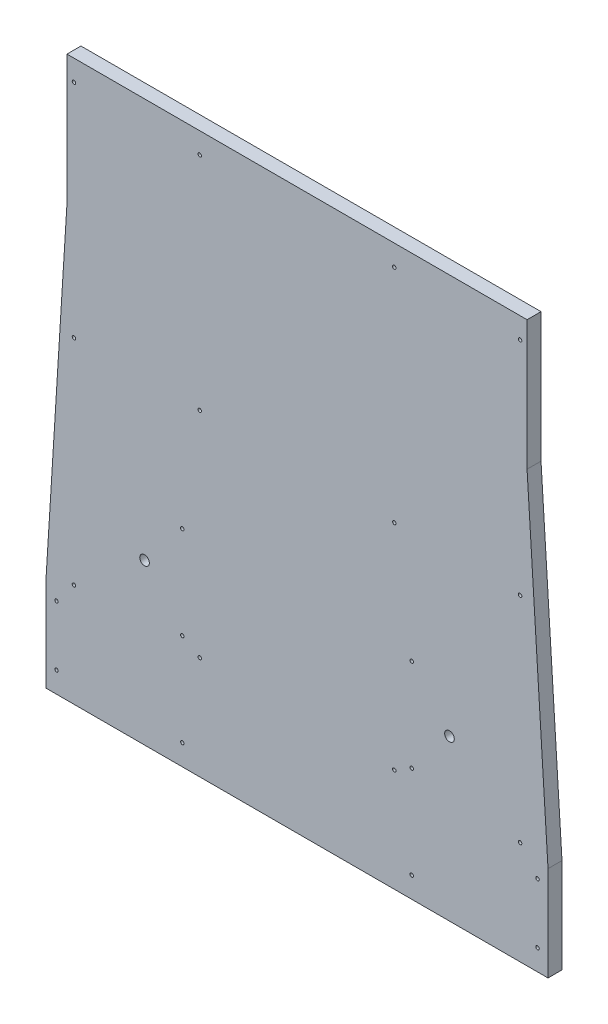
SolidWorks part; units mm, degrees
material "MDF"
ref_plane "Front Plane" through (0, 0, 0) normal (0, 0, 1) x (1, 0, 0)
ref_plane "Top Plane" through (0, 0, 0) normal (0, 1, 0) x (1, 0, 0)
ref_plane "Right Plane" through (0, 0, 0) normal (1, 0, 0) x (0, 0, -1)
sketch "Sketch1" plane through (0, 0, 0) normal (0, 0, 1) x (1, 0, 0)
  line L0 (0, -4273.1683) -> (0, -5592.0408) construction
  line L1 (209.0395, -5469.1795) -> (-209.0395, -5469.1795)
  line L2 (209.0395, -5469.1795) -> (209.0395, -5053.2545)
  line L3 (209.0395, -5053.2545) -> (-209.0395, -5053.2545)
  line L4 (0, -5469.1795) -> (0, -5053.2545) construction
  line L5 (-209.0395, -5469.1795) -> (-209.0395, -5053.2545)
  dimension "D1" = 209.0395
  dimension "D2" = 120.65
  dimension "D3" = 415.925
extrude "Boss-Extrude1" add sketch "Sketch1" along normal blind 12.7
sketch "Sketch2" plane through (0, 0, 0) normal (0, 0, -1) x (-1, 0, 0)
  line L1 (-209.0395, -5469.1795) -> (209.0395, -5469.1795)
  line L2 (-209.0395, -5469.1795) -> (-209.0395, -5548.8695)
  line L3 (-209.0395, -5548.8695) -> (209.0395, -5548.8695)
  line L4 (209.0395, -5469.1795) -> (209.0395, -5548.8695)
  line L8 (209.0395, -5053.2545) -> (209.0395, -5469.1795) construction
  dimension "D1" = 79.69
extrude "Boss-Extrude2" add sketch "Sketch2" against normal through all
sketch "Sketch3" plane through (0, 0, 0) normal (0, 0, -1) x (-1, 0, 0)
  line L1 (209.0395, -5024.8784) -> (-209.0395, -5024.8784)
  line L2 (209.0395, -5024.8784) -> (209.0395, -5053.2545)
  line L3 (209.0395, -5053.2545) -> (-209.0395, -5053.2545)
  line L4 (-209.0395, -5024.8784) -> (-209.0395, -5053.2545)
extrude "Boss-Extrude3" add sketch "Sketch3" against normal through all
sketch "Sketch4" plane through (0, 0, 0) normal (0, 0, -1) x (-1, 0, 0)
  line L0 (209.0388, -5447.3528) -> (228.0888, -5447.3528)
  line L1 (228.0888, -5447.3528) -> (228.0888, -5548.8695)
  line L2 (-209.0395, -5548.8695) -> (209.0395, -5548.8695) construction
  line L3 (228.0888, -5548.8695) -> (209.0395, -5548.8695)
  line L4 (209.0395, -5548.8695) -> (209.0388, -5447.3528)
  line L5 (0, -5562.8703) -> (0, -5024.8784) construction
  line L6 (209.0395, -5024.8784) -> (-209.0395, -5024.8784) construction
  line L7 (-209.0395, -5548.8695) -> (-209.0388, -5447.3528)
  line L8 (-228.0888, -5548.8695) -> (-209.0395, -5548.8695)
  line L9 (-228.0888, -5447.3528) -> (-228.0888, -5548.8695)
  line L10 (-209.0388, -5447.3528) -> (-228.0888, -5447.3528)
extrude "Boss-Extrude4" add sketch "Sketch4" against normal through all
chamfer "Chamfer1" distance 19.05 distance2 304.8 2 edges at (-209.0395, -5447.3528, 6.35) (209.0395, -5447.3528, 6.35) first distance on face at (-218.5641, -5447.3528, 6.35) first distance on face at (218.5641, -5447.3528, 6.35)
sketch "Sketch5" plane through (228.0888, 0, 0) normal (1, 0, 0) x (0, 0, -1)
  line L0 (0, -5447.3417) -> (0, -5548.8695) construction
  line L1 (-12.7, -5548.8695) -> (0, -5548.8695)
  line L2 (-12.7, -5548.8695) -> (-12.7, -5533.4155)
  line L3 (-12.7, -5533.4155) -> (0, -5533.4155)
  line L4 (0, -5548.8695) -> (0, -5533.4155)
extrude "Cut-Extrude1" cut sketch "Sketch5" against normal through all
hole_wizard "5/16 Clearance Hole1" positions "Sketch6" profile "Sketch7" hole size "5/16" standard "ANSI Inch" end condition through all
sketch "Sketch6" plane through (0, 0, 0) normal (0, 0, -1) x (-1, 0, 0)
  point P0 (138.551, -5387.9638)
  point P3 (-138.551, -5387.9638)
sketch "Sketch7" plane through (-138.551, -5387.9638, 0) normal (1, 0, 0) x (0, 1, 0)
  line L0 (0, 0) -> (0, 12.7)
  line L1 (0, 12.7) -> (4.365, 12.7)
  line L2 (4.365, 12.7) -> (4.365, 0)
  line L5 (4.365, 0) -> (0, 0)
  line L11 (0, -6.35) -> (0, 107.95) construction
  dimension "Thru Hole Dia." = 8.73
  dimension "Thru Hole Depth" = 12.7
hole_wizard "Hole1" positions "Sketch8" profile "Sketch9" legacy
sketch "Sketch8" plane through (0, -5562.8703, -19.05) normal (0, 0, -1) x (-1, 0, 0)
  line L0 (218.5638, 29.4548) -> (218.5638, 115.5175) construction
  line L4 (202.6895, 537.9919) -> (202.6895, 97.9067) construction
  line L9 (88.3895, 537.9919) -> (88.3895, 97.9067) construction
  line L13 (104.2638, 29.4548) -> (104.2638, 235.8996) construction
  line L16 (0, 537.9919) -> (0, 29.4548) construction
  point P0 (218.5638, 102.8175)
  point P2 (218.5638, 48.5048)
  point P33 (202.6895, 123.3067)
  point P35 (202.6895, 317.9493)
  point P37 (202.6895, 518.9419)
  point P51 (88.3895, 518.9419)
  point P53 (88.3895, 317.9493)
  point P55 (88.3895, 123.3067)
  point P69 (104.2638, 216.8496)
  point P71 (104.2638, 132.6772)
  point P73 (104.2638, 48.5048)
  point P83 (-104.2638, 48.5048)
  point P84 (-104.2638, 132.6772)
  point P85 (-104.2638, 216.8496)
  point P86 (-88.3895, 123.3067)
  point P87 (-88.3895, 317.9493)
  point P88 (-88.3895, 518.9419)
  point P89 (-202.6895, 518.9419)
  point P90 (-202.6895, 317.9493)
  point P91 (-202.6895, 123.3067)
  point P92 (-218.5638, 48.5048)
  point P93 (-218.5638, 102.8175)
sketch "Sketch9" plane through (-218.5638, -5460.0528, -19.05) normal (1, 0, 0) x (0, 1, 0)
  line L0 (0, 0) -> (0, 51.7539)
  line L1 (0, 51.7539) -> (1.5875, 50.8)
  line L2 (1.5875, 50.8) -> (1.5875, 4.0177)
  line L3 (1.5875, 4.0177) -> (5.08, 0)
  line L4 (5.08, 0) -> (0, 0)
  line L5 (0, -14.3089) -> (0, 102.4216) construction
  line L6 (0, 51.7539) -> (-1.5875, 50.8) construction
  line L7 (-1.5875, 4.0177) -> (-5.08, 0) construction
  dimension "Diameter" = 3.175
  dimension "Depth" = 50.8
  dimension "C-Sink Diameter" = 10.16
  dimension "C-Sink Angle" = 82
  dimension "Drill Angle" = 118
